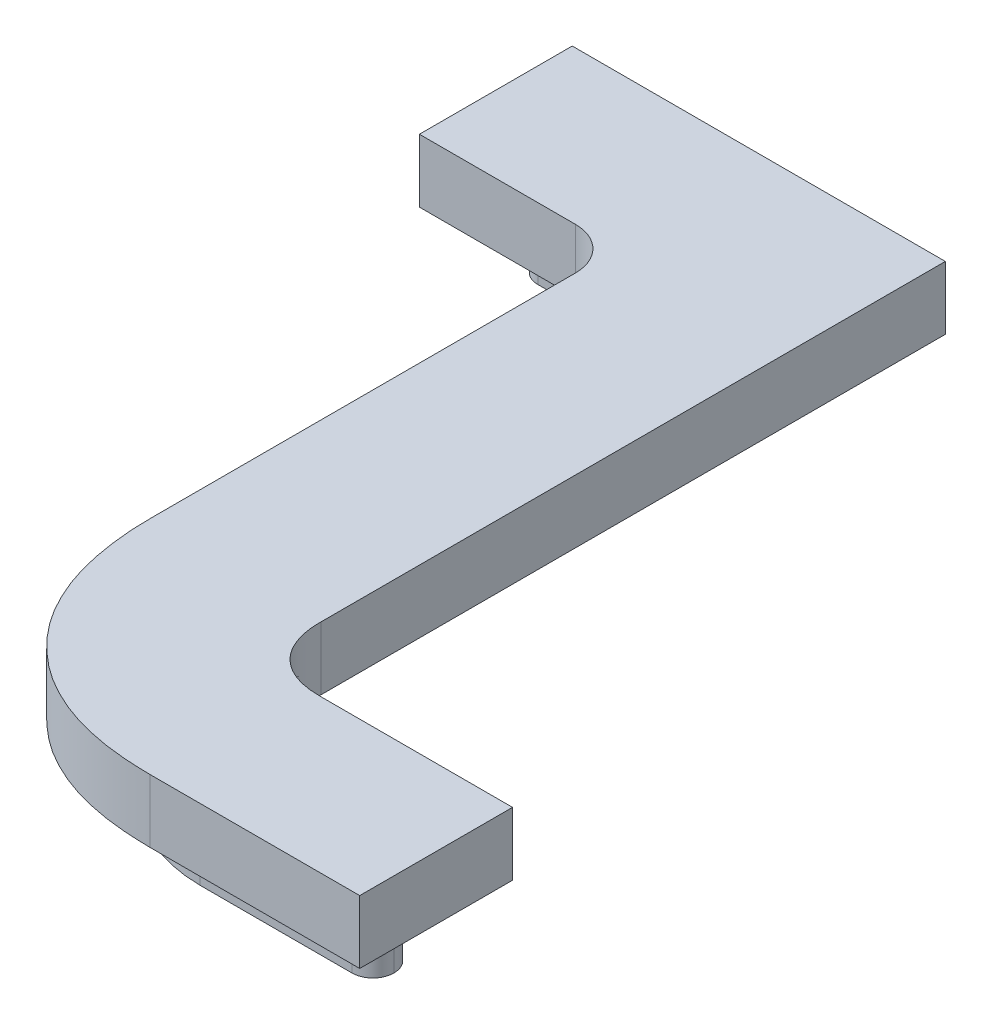
SolidWorks part; units mm, degrees
material "Сосна"
ref_plane "Спереди" through (0, 0, 0) normal (0, 0, 1) x (1, 0, 0)
ref_plane "Сверху" through (0, 0, 0) normal (0, 1, 0) x (1, 0, 0)
ref_plane "Справа" through (0, 0, 0) normal (1, 0, 0) x (0, 0, -1)
sketch "Эскиз l" plane through (0, 0, 0) normal (0, 1, 0) x (1, 0, 0)
  line L0 (0, 163.7019) -> (0, 200)
  line L1 (0, 200) -> (88.6229, 200)
  line L2 (88.6229, 200) -> (88.6229, 51.6827)
  line L3 (103.8472, 36.2981) -> (149.5203, 36.2981)
  line L4 (149.5203, 36.2981) -> (149.5203, 0)
  line L5 (149.5203, 0) -> (99.6806, 0)
  line L6 (47.0764, 53.1651) -> (47.0764, 153.7019)
  line L7 (37.0764, 163.7019) -> (0, 163.7019)
  line L8 (0, -41.4678) -> (0, 218.1094) construction
  line L9 (-35.5991, 0) -> (213.3137, 0) construction
  arc A0 (47.0764, 153.7019) -> (37.0764, 163.7019) centre (37.0764, 153.7019) ccw
  spline S0 degree 3 poles (88.6229, 51.6827) (88.5843, 49.4987) (89.0341, 46.314) (90.7561, 42.5488) (92.5437, 40.2729) (94.8003, 38.4799) (98.4929, 36.6692) (101.6878, 36.2886) (103.8472, 36.2981) knots 0 0 0 0 0.266771 0.385688 0.501834 0.616701 0.734856 1 1 1 1
  spline S1 degree 3 poles (99.6806, 0) (95.788, 0.0566) (90.0492, 0.3542) (82.7564, 1.9134) (77.7224, 3.4207) (73.0474, 5.4358) (68.6596, 7.8427) (64.6571, 10.744) (60.9889, 14.0464) (57.6963, 17.7307) (54.8336, 21.8053) (52.4411, 26.2249) (50.4538, 30.958) (48.934, 36.0358) (47.4906, 43.4419) (47.0224, 49.2206) (47.0764, 53.1651) knots 0 0 0 0 0.13792 0.202112 0.263364 0.323456 0.381806 0.440003 0.497856 0.556061 0.614369 0.673547 0.733455 0.795611 0.860632 1 1 1 1
  dimension "D6" = 10
  dimension "D1" = 163.7019
  dimension "D2" = 36.2981
  dimension "D3" = 36.2981
  dimension "D4" = 47.0764
  dimension "D5" = 41.5465
  dimension "D9" = 149.5203
extrude "l" add sketch "Эскиз l" along normal blind 15
sketch "Эскиз крепежа подсветки" plane through (0, 0, 0) normal (0, 1, 0) x (1, 0, 0)
  line L0 (10, 181.849) -> (67.8532, 181.849)
  line L1 (67.8532, 181.849) -> (67.8532, 49.0404)
  line L2 (98.4233, 18.149) -> (139.5203, 18.149)
  arc A0 (67.8532, 49.0404) -> (98.4233, 18.149) centre (98.7463, 49.0404) ccw
  dimension "D1" = 181.849
  dimension "D2" = 18.149
  dimension "D3" = 67.8532
  dimension "D4" = 139.5203
  dimension "D5" = 10
extrude "Крепёж подсветки" add sketch "Эскиз крепежа подсветки" against normal blind 15 thin thin type mid plane wall 10
fillet "Внешнее скругление под ленту" radius 5 4 edges at (139.5203, -7.5, -13.149) (139.5203, -7.5, -23.149) (10, -7.5, -176.849) (10, -7.5, -186.849)
sketch "Эскиз разметки под шурупы" plane through (0, 0, 0) normal (0, 1, 0) x (1, 0, 0)
  circle A0 centre (15, 181.849) radius 1.5
  circle A1 centre (67.8532, 100) radius 1.5
  circle A2 centre (134.52, 18.149) radius 1.5
  dimension "D1" = 3
  dimension "D2" = 3
  dimension "D3" = 3
  dimension "D4" = 18.149
  dimension "D5" = 134.52
  dimension "D8" = 66.6668
  dimension "D9" = 81.851
  dimension "D6" = 163.7
  dimension "D7" = 119.52
extrude "Разметка под шурупы" cut sketch "Эскиз разметки под шурупы" against normal through all
equation "\"drill\"= 3мм"
equation "\"D1@Эскиз разметки под шурупы\" = \"drill\""
equation "\"D2@Эскиз разметки под шурупы\" = \"drill\""
equation "\"D3@Эскиз разметки под шурупы\" = \"drill\""
